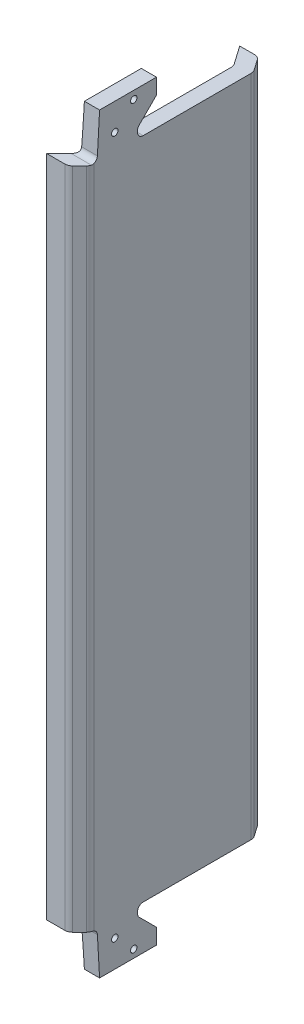
SolidWorks part; units mm, degrees
ref_plane "Front Plane" through (0, 0, 0) normal (0, 0, 1) x (1, 0, 0)
ref_plane "Top Plane" through (0, 0, 0) normal (0, 1, 0) x (1, 0, 0)
ref_plane "Right Plane" through (0, 0, 0) normal (1, 0, 0) x (0, 0, -1)
sketch "Sketch2" plane through (0, 0, 0) normal (0, 1, 0) x (1, 0, 0)
  line L0 (0, 0) -> (50000, 0) construction
  line L1 (0, 0) -> (0, 50000) construction
  line L2 (0, 0) -> (-3.81, -3.81)
  line L3 (-3.81, -3.81) -> (-10.9942, -3.81)
  line L4 (-10.9942, -3.81) -> (-5.08, 2.1042)
  line L5 (-5.08, 2.1042) -> (-5.08, 52.9042)
  line L6 (-5.08, 52.9042) -> (-9.8315, 59.69)
  line L7 (-9.8315, 59.69) -> (-3.6299, 59.69)
  line L8 (-3.6299, 59.69) -> (0, 54.5059)
  line L9 (0, 54.5059) -> (0, 0)
  dimension "D1" = 5.08
  dimension "D2" = 45
  dimension "D3" = 3.81
  dimension "D4" = 50.8
  dimension "D5" = 5.08
  dimension "D6" = 35
  dimension "D7" = 5.08
  dimension "D8" = 63.5
extrude "Boss-Extrude1" add sketch "Sketch2" along normal mid plane 222.25
sketch "Sketch3" plane through (-5.08, 0, 0) normal (-1, 0, 0) x (0, 0, 1)
  line L0 (-78.3042, 0) -> (49921.6958, 0) construction
  line L1 (-59.69, 111.125) -> (-59.69, -111.125) construction
  line L2 (-27.5042, 203.2) -> (-27.5042, -49796.8) construction
  line L3 (-52.9042, 111.125) -> (-2.1042, 111.125) construction
  line L8 (-40.64, 123.19) -> (-46.99, 123.19) construction
  line L9 (-39.37, 111.125) -> (-39.37, 114.3) construction
  line L10 (-39.37, 114.3) -> (-33.02, 120.65) construction
  line L11 (-33.02, 120.65) -> (-33.02, 125.857) construction
  line L12 (-33.02, 125.857) -> (-52.07, 125.857) construction
  line L13 (-52.07, 125.857) -> (-52.9042, 111.125) construction
  line L15 (-39.37, 111.125) -> (-52.9042, 111.125) construction
  line L16 (-40.64, -123.19) -> (-46.99, -123.19) construction
  line L17 (-39.37, -111.125) -> (-52.9042, -111.125) construction
  line L18 (-52.07, -125.857) -> (-52.9042, -111.125) construction
  line L19 (-33.02, -125.857) -> (-52.07, -125.857) construction
  line L20 (-33.02, -120.65) -> (-33.02, -125.857) construction
  line L21 (-39.37, -114.3) -> (-33.02, -120.65) construction
  line L22 (-39.37, -111.125) -> (-39.37, -114.3) construction
  line L23 (-14.3684, -123.19) -> (-8.0184, -123.19) construction
  line L24 (-14.3684, 123.19) -> (-8.0184, 123.19) construction
  line L25 (-15.6384, -111.125) -> (-15.6384, -114.3)
  line L26 (-15.6384, -114.3) -> (-21.9884, -120.65)
  line L27 (-21.9884, -120.65) -> (-21.9884, -125.857)
  line L28 (-21.9884, -125.857) -> (-2.9384, -125.857)
  line L29 (-2.9384, -125.857) -> (-2.1042, -111.125)
  line L30 (-15.6384, -111.125) -> (-2.1042, -111.125)
  line L31 (-15.6384, 111.125) -> (-2.1042, 111.125)
  line L32 (-2.9384, 125.857) -> (-2.1042, 111.125)
  line L33 (-21.9884, 125.857) -> (-2.9384, 125.857)
  line L34 (-21.9884, 120.65) -> (-21.9884, 125.857)
  line L35 (-15.6384, 114.3) -> (-21.9884, 120.65)
  line L36 (-15.6384, 111.125) -> (-15.6384, 114.3)
  circle A0 centre (-46.99, 123.19) radius 3.175 construction
  circle A1 centre (-40.64, 123.19) radius 1.0795 construction
  circle A2 centre (-46.99, 116.84) radius 1.0795 construction
  circle A3 centre (-46.99, -116.84) radius 1.0795 construction
  circle A4 centre (-40.64, -123.19) radius 1.0795 construction
  circle A5 centre (-46.99, -123.19) radius 3.175 construction
  circle A6 centre (-8.0184, -123.19) radius 3.175 construction
  circle A7 centre (-14.3684, -123.19) radius 1.0795 construction
  circle A8 centre (-8.0184, -116.84) radius 1.0795 construction
  circle A9 centre (-8.0184, 116.84) radius 1.0795 construction
  circle A10 centre (-14.3684, 123.19) radius 1.0795 construction
  circle A11 centre (-8.0184, 123.19) radius 3.175 construction
  point P4 (-59.69, 0)
  point P9 (-27.5042, 111.125)
  dimension "D3" = 2.159
  dimension "D4" = 2.159
  dimension "D7" = 6.35
  dimension "D1" = 123.19
  dimension "D2" = 12.7
  dimension "D5" = 6.35
  dimension "D6" = 6.35
  dimension "D8" = 12.7
  dimension "D9" = 20.32
  dimension "D10" = 228.6
  dimension "D11" = 241.3
  dimension "D12" = 125.857
  dimension "D13" = 26.67
  dimension "D14" = 7.62
extrude "Boss-Extrude2" add sketch "Sketch3" against normal up to surface (5.08 mm away) up to face at (0, 0, -27.253)
sketch "Sketch4" plane through (-5.08, 0, 0) normal (-1, 0, 0) x (0, 0, 1)
  circle A0 centre (-40.64, 123.19) radius 1.0795
  circle A1 centre (-46.99, 116.84) radius 1.0795
  circle A2 centre (-40.64, 123.19) radius 3.429
  circle A3 centre (-46.99, 116.84) radius 3.429
  circle A4 centre (-40.64, 123.19) radius 1.0795 construction
  circle A5 centre (-46.99, 116.84) radius 1.0795 construction
  dimension "D1" = 6.858
  dimension "D2" = 6.858
sketch "Sketch5" plane through (-5.08, 0, 0) normal (-1, 0, 0) x (0, 0, 1)
  circle A0 centre (-8.0184, -116.84) radius 1.0795 construction
  circle A1 centre (-14.3684, -123.19) radius 1.0795 construction
  circle A2 centre (-8.0184, 116.84) radius 1.0795 construction
  circle A3 centre (-14.3684, 123.19) radius 1.0795 construction
  circle A8 centre (-40.64, -123.19) radius 1.0795 construction
  circle A9 centre (-46.99, -116.84) radius 1.0795 construction
  circle A11 centre (-46.99, 116.84) radius 1.0795 construction
  circle A12 centre (-40.64, 123.19) radius 1.0795 construction
  circle A13 centre (-40.64, -123.19) radius 1.0795
  circle A14 centre (-46.99, -116.84) radius 1.0795
  circle A15 centre (-46.99, 116.84) radius 1.0795
  circle A16 centre (-40.64, 123.19) radius 1.0795
  circle A17 centre (-8.0184, -116.84) radius 1.0795
  circle A18 centre (-14.3684, -123.19) radius 1.0795
  circle A19 centre (-8.0184, 116.84) radius 1.0795
  circle A20 centre (-14.3684, 123.19) radius 1.0795
extrude "Cut-Extrude1" cut sketch "Sketch5" against normal through all
fillet "Fillet2" radius 1.905 6 edges at (-2.54, -114.3, -15.6384) (-2.54, -111.125, -15.6384) (-2.54, 114.3, -15.6384) (-2.54, 111.125, -15.6384) (-2.54, 111.125, -2.1042) (-2.54, -111.125, -2.1042)
fillet "Fillet3" radius 2.54 6 edges at (-3.6299, 0, -59.69) (-3.81, 0, 3.81) (0, 0, -54.5059) (0, 0, 0) (-5.08, 0, -52.9042) (-5.08, 0, -2.1042)
equation "\"D4@Sketch3\"=\"D3@Sketch3\""
equation "\"D8@Sketch3\"=\"D2@Sketch3\""
equation "\"D2@Sketch4\"=\"D1@Sketch4\""
